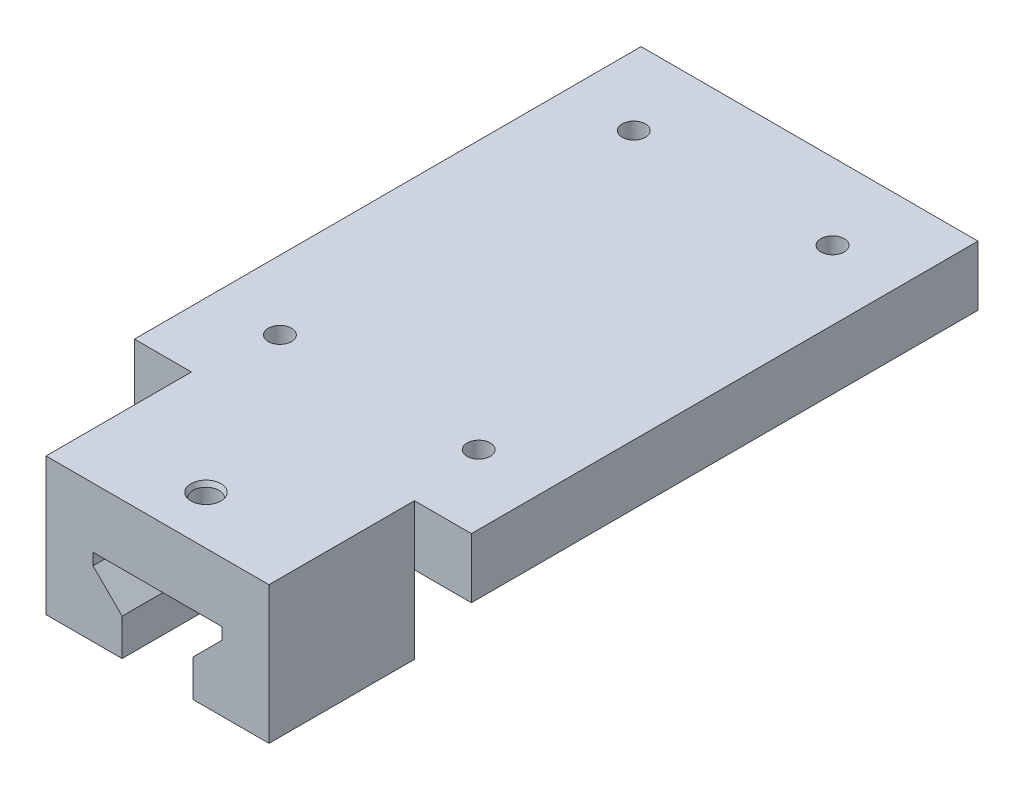
SolidWorks part; units mm, degrees
ref_plane "Front Plane" through (0, 0, 0) normal (0, 0, 1) x (1, 0, 0)
ref_plane "Top Plane" through (0, 0, 0) normal (0, 1, 0) x (1, 0, 0)
ref_plane "Right Plane" through (0, 0, 0) normal (1, 0, 0) x (0, 0, -1)
sketch "Sketch1" plane through (0, 0, 0) normal (0, 0, 1) x (1, 0, 0)
  line L0 (-7, 0) -> (7, 0) construction
  line L1 (-7, 0) -> (-7, 8) construction
  line L2 (-7, 8) -> (-13, 14) construction
  line L3 (-13, 14) -> (-13, 16) construction
  line L4 (13, 14) -> (7, 8) construction
  line L5 (7, 8) -> (7, 0) construction
  line L6 (-7.3, 0.3) -> (-7.3, 7.8757)
  line L10 (7.3, 7.8757) -> (7.3, 0.3)
  line L11 (7.3, 0.3) -> (23, 0.3)
  line L12 (23, 0.3) -> (23, 28.65)
  line L13 (23, 28.65) -> (-23, 28.65)
  line L14 (-23, 28.65) -> (-23, 0.3)
  line L15 (-23, 0.3) -> (-7.3, 0.3)
  line L16 (-13, 16) -> (13, 16) construction
  line L17 (13, 16) -> (13, 14) construction
  line L18 (-7.3, 7.8757) -> (-13.3, 13.8757)
  line L19 (-13.3, 13.8757) -> (-13.3, 16.3)
  line L20 (-13.3, 16.3) -> (13.3, 16.3)
  line L21 (13.3, 16.3) -> (13.3, 13.8757)
  line L22 (13.3, 13.8757) -> (7.3, 7.8757)
  point P4 (0, 0)
  point P22 (0, 16.3)
  dimension "D1" = 14
  dimension "D2" = 8
  dimension "D3" = 26
  dimension "D4" = 0.3
  dimension "D5" = 0.3
  dimension "D6" = 0.3
  dimension "D7" = 0.3
  dimension "D8" = 2
  dimension "D9" = 0.3
  dimension "D10" = 0.3
  dimension "D11" = 46
  dimension "D12" = 6
  dimension "D13" = 0.3
  dimension "D14" = 0.3
  dimension "D15" = 12.35
extrude "Boss-Extrude1" add sketch "Sketch1" along normal blind 30
sketch "Sketch4" plane through (0, 28.65, 0) normal (0, 1, 0) x (1, 0, 0)
  line L5 (23, -30) -> (-23, -30) construction
  point P4 (0, -20)
  point P22 (0, 0)
  dimension "D1" = 10
hole_wizard "Hole1" positions "Sketch4" profile "Sketch3" legacy end condition up to next
sketch "Sketch3" plane through (0, 28.65, 20) normal (1, 0, 0) x (0, 0, 1)
  line L0 (0, 0) -> (0, 12.35)
  line L1 (0, 12.35) -> (2.7, 12.35)
  line L2 (2.7, 12.35) -> (2.7, 1)
  line L3 (2.7, 1) -> (3.1, 1)
  line L4 (3.1, 1) -> (3.1, 0)
  line L5 (3.1, 0) -> (0, 0)
  line L6 (0, 110) -> (0, -10) construction
  dimension "Diameter" = 5.4
  dimension "Depth" = 12.35
  dimension "C-Bore Diameter" = 6.2
  dimension "C-Bore Depth" = 1
chamfer "Chamfer1" distance 1 distance2 0.4 1 edges at (0, 27.65, 23.1) first distance on face at (0, 27.65, 23.1)
sketch "Sketch5" plane through (0, 28.65, 0) normal (0, 1, 0) x (1, 0, 0)
  line L1 (-34.75, 0) -> (34.75, 0)
  line L2 (-34.75, 0) -> (-34.75, 104.5)
  line L3 (-34.75, 104.5) -> (34.75, 104.5)
  line L4 (34.75, 0) -> (34.75, 104.5)
  point P4 (0, 0)
  dimension "D1" = 104.5
  dimension "D2" = 69.5
extrude "Boss-Extrude2" add sketch "Sketch5" against normal up to surface (12.35 mm away) up to face at (0, 16.3, 22.7)
sketch "Sketch8" plane through (0, 16.3, 0) normal (0, -1, 0) x (-1, 0, 0)
  line L0 (-20.5, 88.75) -> (20.5, 88.75) construction
  line L1 (20.5, 88.75) -> (20.5, 15.75) construction
  line L2 (20.5, 15.75) -> (-20.5, 15.75) construction
  line L3 (-20.5, 15.75) -> (-20.5, 88.75) construction
  line L5 (34.75, 0) -> (34.75, 104.5) construction
  point P0 (-20.5, 88.75)
  point P2 (20.5, 88.75)
  point P4 (-20.5, 15.75)
  point P6 (20.5, 15.75)
  point P19 (0, 15.75)
  point P23 (34.75, 52.25)
  point P24 (20.5, 52.25)
  dimension "D1" = 41
  dimension "D2" = 73
hole_wizard "CBORE for M4 SHCS1" positions "Sketch8" profile "Sketch7" counterbore size "M4" standard "ANSI Metric" end condition through all
sketch "Sketch7" plane through (20.5, 16.3, -88.75) normal (1, 0, 0) x (0, 0, -1)
  line L0 (0, 0) -> (0, 12.35)
  line L1 (0, 12.35) -> (2.4, 12.35)
  line L3 (2.4, 12.35) -> (2.4, 4)
  line L4 (2.4, 4) -> (4, 4)
  line L5 (4, 4) -> (4, 0)
  line L7 (4, 0) -> (0, 0)
  line L11 (0, -6.35) -> (0, 107.95) construction
  dimension "Thru Hole Dia." = 4.8
  dimension "Thru Hole Depth" = 12.35
  dimension "C'Bore Dia." = 8
  dimension "C'Bore Depth" = 4
